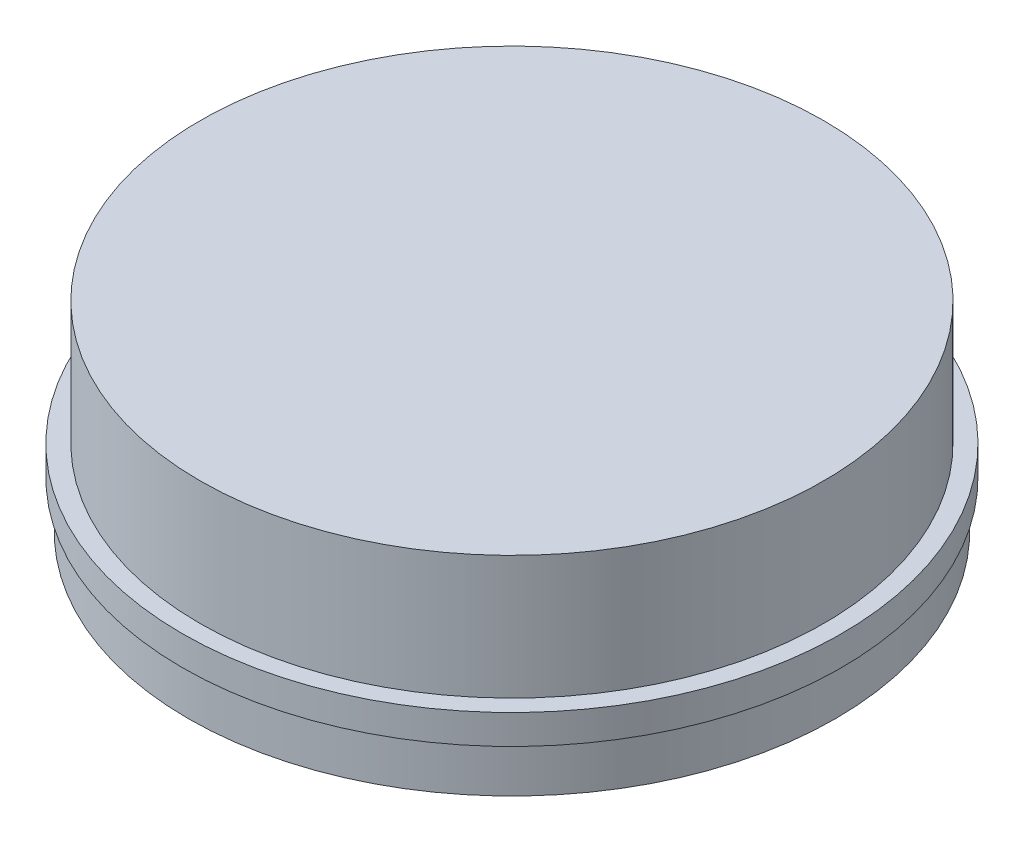
SolidWorks part; units mm, degrees
ref_plane "Front Plane" through (0, 0, 0) normal (0, 0, 1) x (1, 0, 0)
ref_plane "Top Plane" through (0, 0, 0) normal (0, 1, 0) x (1, 0, 0)
ref_plane "Right Plane" through (0, 0, 0) normal (1, 0, 0) x (0, 0, -1)
sketch "Sketch1" plane through (0, 0, 0) normal (0, 1, 0) x (1, 0, 0)
  circle A0 centre (0, 0) radius 26.5
  circle A1 centre (0, 0) radius 28
  circle A2 centre (0, 0) radius 27.5
  dimension "D1" = 53
  dimension "D2" = 56
  dimension "D3" = 55
extrude "Boss-Extrude1" add sketch "Sketch1" along normal blind 10.5 contours A0 region at (0, 0, 0)
extrude "Boss-Extrude2" add sketch "Sketch1<3>" against normal blind 2.5 contours A1 A2 | A2 A0 | A0 region at (0, 0, 0) region at (-27.9208, 0, 0) region at (-26.7222, 0, 0)
sketch "Sketch1<3>" plane through (0, 0, 0) normal (0, 1, 0) x (1, 0, 0) same geometry as "Sketch1"
extrude "Boss-Extrude3" add sketch "Sketch1<4>" against normal blind 6.5 contours A2 A0 region at (-26.7222, 0, 0)
sketch "Sketch1<4>" plane through (0, 0, 0) normal (0, 1, 0) x (1, 0, 0) same geometry as "Sketch1"
ref_axis "Axis1" through (0, 10.5, 0) along (0, -1, 0)
